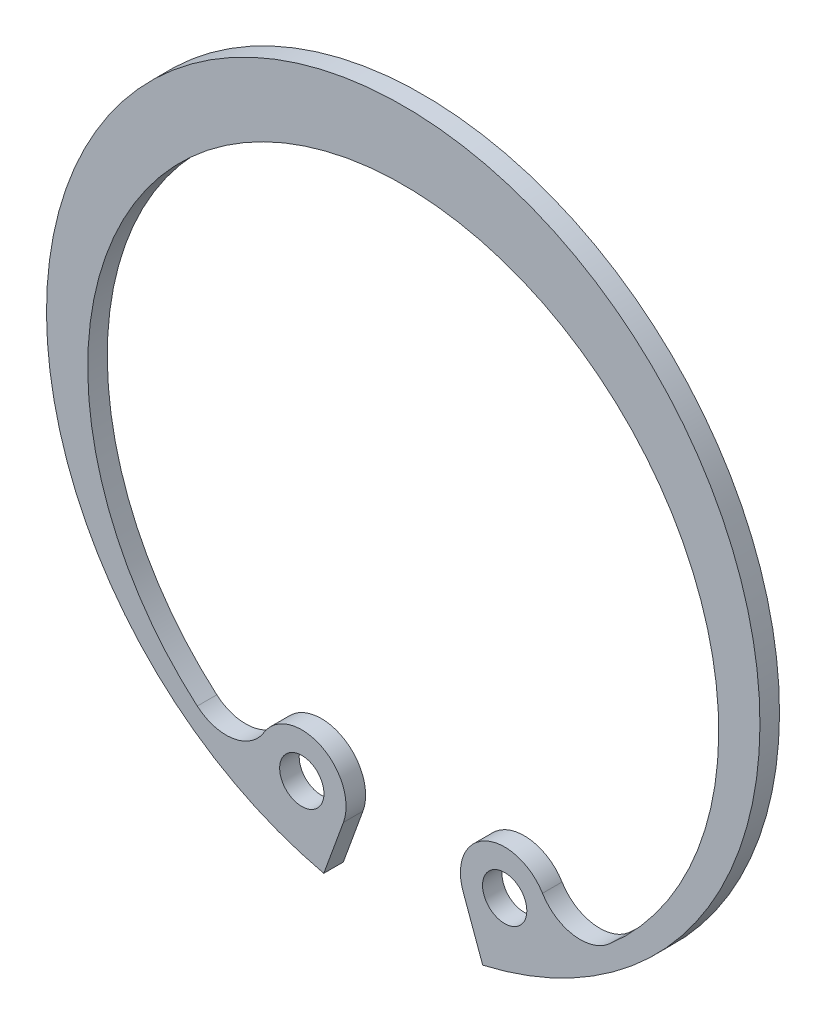
SolidWorks part; units mm, degrees
ref_plane "Front" through (0, 0, 0) normal (0, 0, 1) x (1, 0, 0)
ref_plane "Top" through (0, 0, 0) normal (0, 1, 0) x (1, 0, 0)
ref_plane "Right" through (0, 0, 0) normal (1, 0, 0) x (0, 0, -1)
ref_axis "Center Axis" through (0, 0, 1.5888) along (0, 0, -1)
sketch "Sketch1" plane through (0, 0, 0) normal (0, 0, 1) x (1, 0, 0)
  circle A0 centre (0, 0) radius 21
  dimension "D1" = 42
extrude "Extrude1" add sketch "Sketch1" along normal blind 1.15
ref_plane "Reference Plane for Front Recess" through (0, 0, 1.15) normal (0, 0, 1) x (1, 0, 0)
sketch "Sketch34" plane through (0, 0, 1.15) normal (0, 0, 1) x (1, 0, 0)
  line L0 (0, 0) -> (0, -10.6398) construction
  line L1 (0, 0) -> (-3.8763, -10.6501) construction
  line L2 (0, 0) -> (3.8763, -10.6501) construction
  line L3 (-3.5223, -17.2987) -> (-4.6774, -20.4725)
  line L4 (3.5223, -17.2987) -> (4.6774, -20.4725)
  circle A1 centre (0, 0) radius 21 construction
  arc A2 (4.6774, -20.4725) -> (-4.6774, -20.4725) centre (0, 0) ccw
  circle A3 centre (0, -1.6002) radius 15.9658 construction
  circle A4 centre (5.9717, -16.4072) radius 1.3033
  circle A5 centre (-5.9717, -16.4072) radius 1.3033
  arc A6 (-3.5223, -17.2987) -> (-8.1976, -15.0506) centre (-5.9717, -16.4072) ccw
  arc A7 (3.5223, -17.2987) -> (8.1976, -15.0506) centre (5.9717, -16.4072) cw
  arc A9 (-12.1252, -15.6685) -> (-8.1976, -15.0506) centre (-10.4234, -13.694) ccw
  arc A12 (12.1252, -15.6685) -> (8.1976, -15.0506) centre (10.4234, -13.694) cw
  arc A14 (12.1252, -15.6685) -> (-12.1252, -15.6685) centre (0, -1.6002) ccw
  point P0 (0, -1.6002)
  dimension "D2" = 5.2133
  dimension "D5" = 2.6067
  dimension "D4" = 37.145
  dimension "D1" = 1.6002
  dimension "D3" = 40
extrude "056-250 Snap Ring" add sketch "Sketch34" along normal blind 1.15
sketch "Sketch35" plane through (0, 0, 0) normal (0, 0, -1) x (-1, 0, 0)
  circle A1 centre (0, 0) radius 21
  circle A2 centre (0, 0) radius 21
  dimension "D1" = 0
extrude "Cut-Extrude1" cut sketch "Sketch35" against normal blind 1.15
